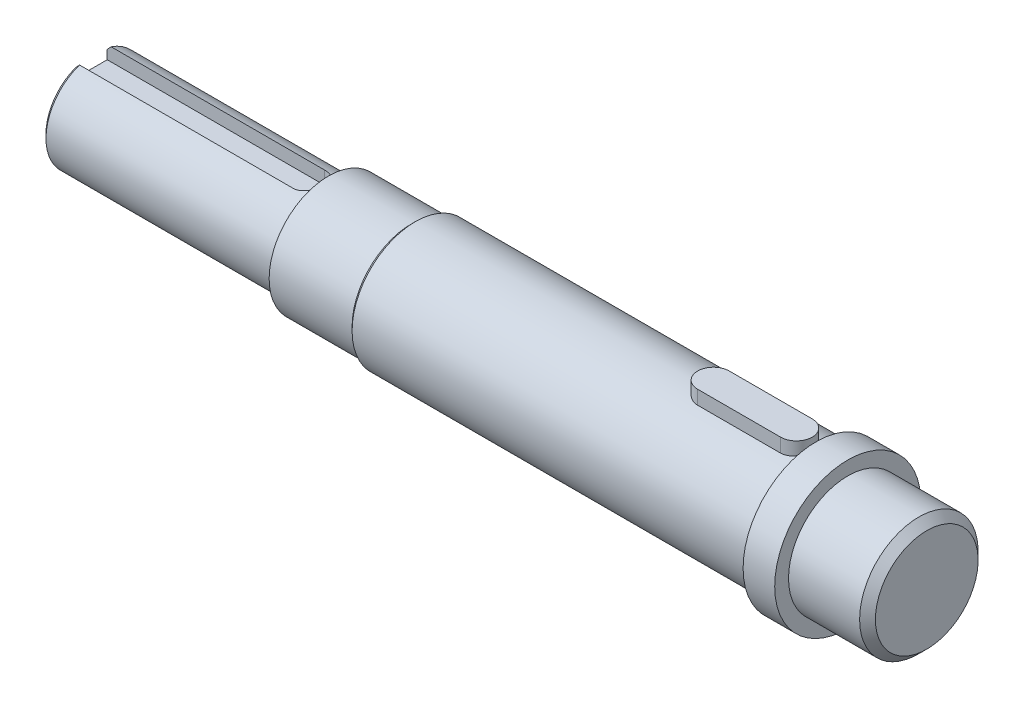
SolidWorks part; units mm, degrees
material "Alloy Steel"
ref_plane "Front Plane" through (0, 0, 0) normal (0, 0, 1) x (1, 0, 0)
ref_plane "Top Plane" through (0, 0, 0) normal (0, 1, 0) x (1, 0, 0)
ref_plane "Right Plane" through (0, 0, 0) normal (1, 0, 0) x (0, 0, -1)
sketch "Sketch1" plane through (0, 0, 0) normal (0, 0, 1) x (1, 0, 0)
  line L0 (-81.1443, 0) -> (182.2806, 0) construction
  line L1 (-74.0882, 0) -> (-74.0882, 11.5)
  line L2 (-73.0882, 12.5) -> (-15.0882, 12.5)
  line L3 (-14.0882, 13.5) -> (-14.0882, 15)
  line L4 (6.9118, 15) -> (-14.0882, 15)
  line L5 (6.9118, 16) -> (109.4118, 16)
  line L6 (-74.0882, 11.5) -> (-73.0882, 12.5)
  line L8 (-15.0882, 12.5) -> (-14.0882, 13.5)
  line L11 (6.9118, 16) -> (6.9118, 15)
  line L13 (-74.0882, 0) -> (137.4118, 0)
  line L16 (109.4118, 16) -> (109.4118, 18.5)
  line L17 (109.4118, 18.5) -> (117.4118, 18.5)
  line L18 (117.4118, 18.5) -> (117.4118, 15)
  line L19 (117.4118, 15) -> (137.4118, 15)
  line L20 (137.4118, 15) -> (137.4118, 0)
  point P4 (-74.0882, 12.5)
  point P6 (-14.0882, 12.5)
  dimension "D2" = 25
  dimension "D3" = 60
  dimension "D4" = 102.5
  dimension "D5" = 21
  dimension "D10" = 8
  dimension "D11" = 32
  dimension "D12" = 30
  dimension "D13" = 20
  dimension "D14" = 30
revolve "Revolve1" add sketch "Sketch1" angle 360 about L0
sketch "Sketch2" plane through (0, 0, 0) normal (0, 1, 0) x (1, 0, 0)
  line L0 (-74.7487, 0) -> (-19.0882, 0) construction
  line L1 (-74.7487, 4) -> (-19.0882, 4)
  line L2 (-74.7487, -4) -> (-19.0882, -4)
  line L3 (-15.0882, -12.5) -> (-15.0882, 12.5) construction
  arc A0 (-74.7487, 4) -> (-74.7487, -4) centre (-74.7487, 0) ccw
  arc A1 (-19.0882, -4) -> (-19.0882, 4) centre (-19.0882, 0) ccw
  point P3 (-46.9185, 0)
  dimension "D1" = 8
extrude "Cut-Extrude1" cut sketch "Sketch2" against normal blind 4 from offset 12.5
chamfer "Chamfer1" distance 2 angle 45 1 edges at (137.4118, 0, 15)
sketch "Sketch3" plane through (0, 0, 0) normal (0, 1, 0) x (1, 0, 0)
  line L0 (83.4118, 0) -> (104.4118, 0) construction
  line L1 (83.4118, 4) -> (104.4118, 4)
  line L2 (83.4118, -4) -> (104.4118, -4)
  line L5 (109.4118, 18.5) -> (109.4118, -18.5) construction
  arc A0 (83.4118, 4) -> (83.4118, -4) centre (83.4118, 0) ccw
  arc A1 (104.4118, -4) -> (104.4118, 4) centre (104.4118, 0) ccw
  point P3 (93.9118, 0)
  dimension "D2" = 5
  dimension "D1" = 8
  dimension "D3" = 21
extrude "Cut-Extrude2" cut sketch "Sketch3" against normal blind 5 from offset 16
sketch "Sketch4" plane through (0, 11, 0) normal (0, 1, 0) x (1, 0, 0)
  line L2 (83.4118, -4) -> (104.4118, -4)
  line L3 (104.4118, 4) -> (83.4118, 4)
  line L4 (83.4118, -4) -> (104.4118, -4)
  line L5 (104.4118, 4) -> (83.4118, 4)
  arc A2 (83.4118, 4) -> (83.4118, -4) centre (83.4118, 0) ccw
  arc A3 (104.4118, -4) -> (104.4118, 4) centre (104.4118, 0) ccw
  arc A4 (83.4118, 4) -> (83.4118, -4) centre (83.4118, 0) ccw
  arc A5 (104.4118, -4) -> (104.4118, 4) centre (104.4118, 0) ccw
  dimension "D1" = 0
extrude "Boss-Extrude1" add sketch "Sketch4" along normal blind 8 separate body
chamfer "Chamfer2" distance 1 angle 45 1 edges at (6.9118, 0, 16)
